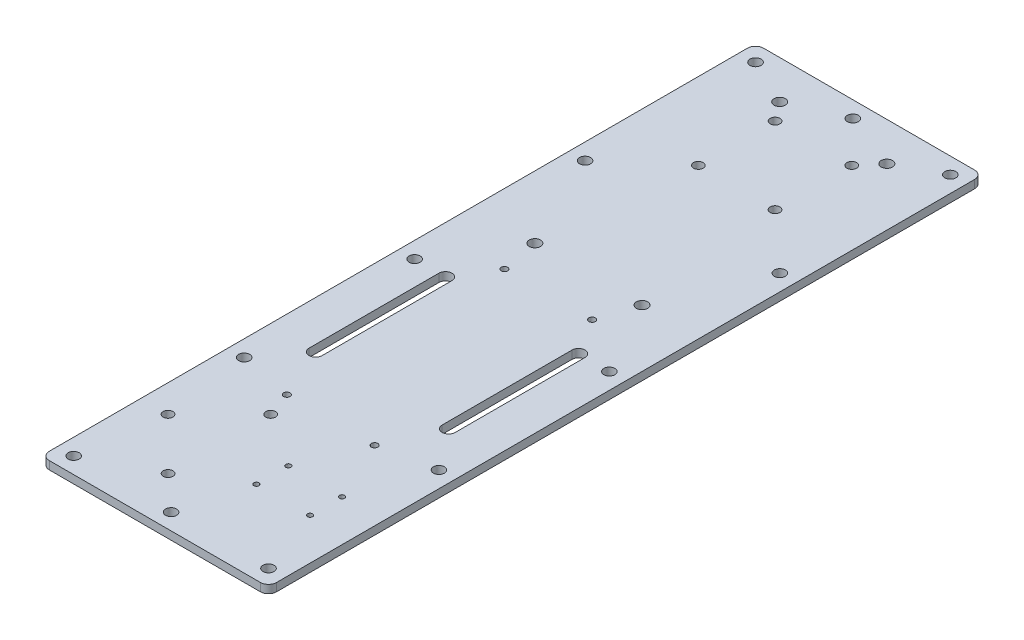
SolidWorks part; units mm, degrees
ref_plane "Front Plane" through (0, 0, 0) normal (0, 0, 1) x (1, 0, 0)
ref_plane "Top Plane" through (0, 0, 0) normal (0, 1, 0) x (1, 0, 0)
ref_plane "Right Plane" through (0, 0, 0) normal (1, 0, 0) x (0, 0, -1)
sketch "Sketch2" plane through (0, 0, 0) normal (0, 1, 0) x (1, 0, 0)
  line L0 (-44.45, 0) -> (44.45, 0) construction
  line L1 (-41.275, 139.7) -> (41.275, 139.7)
  line L2 (-44.45, 136.525) -> (-44.45, -136.525)
  line L3 (-41.275, -139.7) -> (41.275, -139.7)
  line L4 (44.45, 136.525) -> (44.45, -136.525)
  line L5 (0, 139.7) -> (0, -139.7) construction
  arc A0 (-44.45, -136.525) -> (-41.275, -139.7) centre (-41.275, -136.525) ccw
  arc A1 (41.275, -139.7) -> (44.45, -136.525) centre (41.275, -136.525) ccw
  arc A2 (41.275, 139.7) -> (44.45, 136.525) centre (41.275, 136.525) cw
  arc A3 (-41.275, 139.7) -> (-44.45, 136.525) centre (-41.275, 136.525) ccw
  point P8 (0, 0)
  point P13 (-44.45, -139.7)
  point P16 (44.45, -139.7)
  point P21 (-44.45, 139.7)
  dimension "D3" = 3.175
  dimension "D1" = 279.4
  dimension "D2" = 88.9
extrude "Plate Thickness" add sketch "Sketch2" along normal blind 3.175 contours L2 A0 L3 A1 L4 A2 L1 A3
sketch "Sketch3" plane through (0, 3.175, 0) normal (0, 1, 0) x (1, 0, 0)
  line L0 (-44.45, 136.525) -> (-44.45, -136.525) construction
  line L1 (-41.275, 139.7) -> (41.275, 139.7) construction
  line L4 (0, 139.7) -> (0, -139.7) construction
  line L5 (-41.275, -139.7) -> (41.275, -139.7) construction
  circle A0 centre (-38.1, 133.35) radius 2.159
  circle A1 centre (-38.1, 66.675) radius 2.159
  circle A2 centre (-38.1, -66.675) radius 2.159
  circle A3 centre (-38.1, -133.35) radius 2.159
  circle A4 centre (38.1, -133.35) radius 2.159
  circle A5 centre (38.1, -66.675) radius 2.159
  circle A6 centre (38.1, 66.675) radius 2.159
  circle A7 centre (38.1, 133.35) radius 2.159
  circle A8 centre (0, 133.35) radius 2.159
  circle A9 centre (0, -133.35) radius 2.159
  circle A10 centre (-38.1, 0) radius 2.159
  circle A11 centre (38.1, 0) radius 2.159
  dimension "D1" = 4.318
  dimension "D4" = 4.318
  dimension "D2" = 6.35
  dimension "D3" = 6.35
  dimension "D5" = 66.675
  dimension "D6" = 6.35
  dimension "D7" = 66.675
extrude "Mounting holes" cut sketch "Sketch3" against normal through all
sketch "Sketch4" plane through (0, 3.175, 0) normal (0, 1, 0) x (1, 0, 0)
  line L0 (-19.9374, 28.8942) -> (21.9726, 28.8942) construction
  line L1 (1.0176, 0) -> (1.0176, 139.7) construction
  circle A0 centre (-19.9374, 124.6522) radius 2.2225
  circle A1 centre (-19.9374, 28.8942) radius 2.2225
  circle A2 centre (21.9726, 28.8942) radius 2.2225
  circle A3 centre (21.9726, 124.6522) radius 2.2225
  point P13 (1.0176, 28.8942)
  dimension "D1" = 4.445
  dimension "D2" = 95.758
  dimension "D3" = 41.91
extrude "Jetson Holes (w/ mount)" cut sketch "Sketch4" against normal through all
sketch "Sketch5" plane through (0, 3.175, 0) normal (0, 1, 0) x (1, 0, 0)
  circle A1 centre (-14.3419, 117.2351) radius 1.905
  circle A3 centre (15.6555, 117.2351) radius 1.905
  circle A4 centre (15.6555, 87.2377) radius 1.905
  circle A5 centre (-14.3419, 87.2377) radius 1.905
  dimension "D1" = 3.81
  dimension "D2" = 29.9974
  dimension "D3" = 29.9974
extrude "PDB holes" cut sketch "Sketch5" against normal through all
sketch "Sketch6" plane through (0, 3.175, 0) normal (0, 1, 0) x (1, 0, 0)
  circle A6 centre (-13.6622, -120.8784) radius 1.905
  circle A7 centre (-13.6622, -80.7464) radius 1.905
  circle A8 centre (-33.7282, -100.8124) radius 1.905
  point P8 (-17.3072, -59.9885)
  point P11 (0, 0)
  point P12 (-17.3072, -22.1289)
  point P15 (0, 0)
  point P16 (-32.0724, -38.7871)
  point P17 (-31.5045, -38.9764)
  dimension "D5" = 40.132
  dimension "D6" = 20.066
  dimension "D7" = 20.066
extrude "Lidar Holes" cut sketch "Sketch6" against normal through all
sketch "Sketch7" plane through (0, 3.175, 0) normal (0, 1, 0) x (1, 0, 0)
  line L0 (0, 139.7) -> (0, -139.7) construction
  line L1 (-41.275, 139.7) -> (41.275, 139.7) construction
  line L2 (-41.275, -139.7) -> (41.275, -139.7) construction
  line L3 (17.145, 14.1724) -> (-17.145, 14.1724) construction
  circle A0 centre (-17.145, 14.1724) radius 1.27
  circle A1 centre (-17.145, -70.9176) radius 1.27
  circle A2 centre (17.145, -70.9176) radius 1.27
  circle A3 centre (17.145, 14.1724) radius 1.27
  point P14 (0, 14.1724)
  dimension "D1" = 2.54
  dimension "D2" = 85.09
  dimension "D3" = 34.29
extrude "PixHawk Holes" cut sketch "Sketch7" against normal through all
sketch "Sketch8" plane through (0, 3.175, 0) normal (0, 1, 0) x (1, 0, 0)
  line L0 (0, 139.7) -> (0, -115.5095) construction
  line L1 (-41.275, 139.7) -> (41.275, 139.7) construction
  line L2 (-26.035, -0.006) -> (-26.035, -50.806) construction
  line L3 (-23.495, -0.006) -> (-23.495, -50.806)
  line L4 (-28.575, -0.006) -> (-28.575, -50.806)
  line L5 (26.035, -0.006) -> (26.035, -50.806) construction
  line L6 (23.495, -0.006) -> (23.495, -50.806)
  line L7 (28.575, -0.006) -> (28.575, -50.806)
  arc A0 (-23.495, -0.006) -> (-28.575, -0.006) centre (-26.035, -0.006) ccw
  arc A1 (-28.575, -50.806) -> (-23.495, -50.806) centre (-26.035, -50.806) ccw
  arc A2 (23.495, -0.006) -> (28.575, -0.006) centre (26.035, -0.006) cw
  arc A3 (28.575, -50.806) -> (23.495, -50.806) centre (26.035, -50.806) cw
  point P7 (-26.035, -25.406)
  point P14 (26.035, -25.406)
  dimension "D1" = 50.8
  dimension "D2" = 5.08
  dimension "D3" = 26.035
extrude "Battery Holes" cut sketch "Sketch8" against normal through all
sketch "Sketch9" plane through (0, 0, 0) normal (0, -1, 0) x (1, 0, 0)
  circle A0 centre (7.2431, 107.2269) radius 1
  circle A1 centre (28.2431, 107.2269) radius 1
  circle A2 centre (7.2431, 94.7269) radius 1
  circle A3 centre (28.2431, 94.7269) radius 1
  point P4 (0, 0)
  point P5 (30.9992, 113.2793)
  point P8 (0, 0)
  point P9 (7.2431, 94.7269)
  point P12 (0, 0)
  point P13 (30.9992, 94.7269)
  dimension "D1" = 21
  dimension "D2" = 12.5
  dimension "D3" = 21
extrude "Ventral Boardcam Holes" cut sketch "Sketch9" against normal through all
